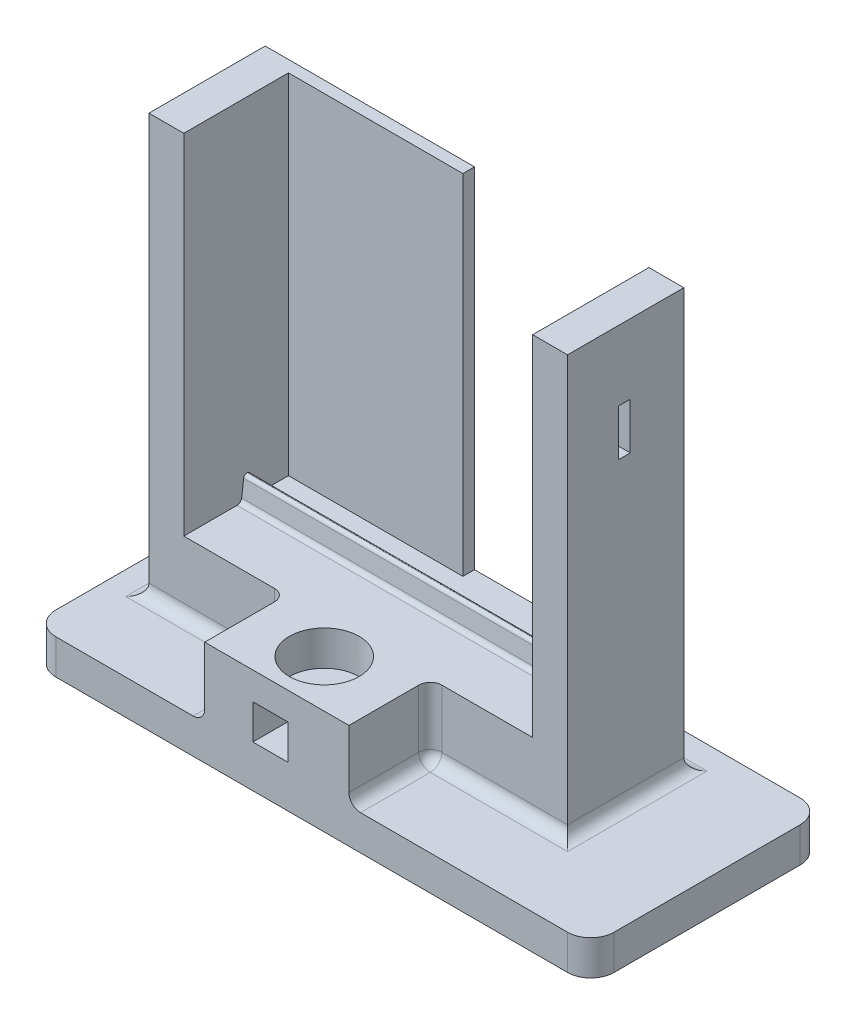
SolidWorks part; units mm, degrees
ref_plane "Front Plane" through (0, 0, 0) normal (0, 0, 1) x (1, 0, 0)
ref_plane "Top Plane" through (0, 0, 0) normal (0, 1, 0) x (1, 0, 0)
ref_plane "Right Plane" through (0, 0, 0) normal (1, 0, 0) x (0, 0, -1)
sketch "Sketch1" plane through (0, 0, 0) normal (0, 1, 0) x (1, 0, 0)
  line L1 (-120, -50) -> (120, -50)
  line L2 (-120, -50) -> (-120, 50)
  line L3 (-120, 50) -> (120, 50)
  line L4 (120, -50) -> (120, 50)
  line L5 (-120, -50) -> (120, 50) construction
  line L6 (-120, 50) -> (120, -50) construction
  point P0 (0, 0)
  dimension "D1" = 240
  dimension "D2" = 100
extrude "Boss-Extrude1" add sketch "Sketch1" along normal blind 15
sketch "Sketch5" plane through (0, 15, 0) normal (0, 1, 0) x (1, 0, 0)
  line L0 (-105, 35) -> (-90, 35)
  line L2 (-105, -15) -> (-90, -15)
  line L4 (-90, 35) -> (-90, -15)
  line L7 (60, 35) -> (60, -15)
  line L10 (60, 35) -> (75, 35)
  line L11 (75, 35) -> (75, -15)
  line L12 (75, -15) -> (60, -15)
  line L13 (-105, 35) -> (-105, -15)
  dimension "D1" = 50
  dimension "D2" = 15
  dimension "D3" = 50
  dimension "D5" = 15
extrude "Boss-Extrude4" add sketch "Sketch5" along normal blind 180
sketch "Sketch12" plane through (0, 15, 0) normal (0, 1, 0) x (1, 0, 0)
  line L0 (60, 35) -> (60, -15) construction
  line L1 (-90, 35) -> (60, 35)
  line L2 (-90, 35) -> (-90, -15)
  line L3 (-90, -15) -> (60, -15)
  line L4 (60, 35) -> (60, -15)
  dimension "D1" = 50
extrude "Boss-Extrude7" add sketch "Sketch12" along normal blind 30
fillet "Fillet1" radius 5 1 edges at (-105, 15, -10)
fillet "Fillet4" radius 5 1 edges at (-17.5, 15, -35)
fillet "Fillet10" radius 5 1 edges at (75, 15, -12.5)
sketch "Sketch15" plane through (0, 15, 0) normal (0, 1, 0) x (1, 0, 0)
  line L0 (-110, -15) -> (80, -15) construction
  line L1 (-15, -15) -> (16, -15)
  line L2 (-15, -15) -> (-46, -15)
  line L3 (-46, -15) -> (-46, -50)
  line L4 (16, -15) -> (16, -50)
  line L5 (-46, -50) -> (16, -50)
  dimension "D1" = 62
  dimension "D2" = 31
  dimension "D3" = 35
extrude "Boss-Extrude8" add sketch "Sketch15" along normal blind 30
sketch "Sketch17" plane through (0, 45, 0) normal (0, 1, 0) x (1, 0, 0)
  circle A0 centre (-15, -29.6274) radius 15
  dimension "D2" = 30
extrude "Cut-Extrude1" cut sketch "Sketch17" against normal blind 15
sketch "Sketch18" plane through (0, 0, 50) normal (0, 0, 1) x (1, 0, 0)
  line L3 (-25.2921, 18.1748) -> (-10.2921, 18.1748)
  line L4 (-25.2921, 18.1748) -> (-25.2921, 33.1748)
  line L5 (-25.2921, 33.1748) -> (-10.2921, 33.1748)
  line L6 (-10.2921, 18.1748) -> (-10.2921, 33.1748)
  line L7 (-25.2921, 18.1748) -> (-10.2921, 33.1748) construction
  line L8 (-25.2921, 33.1748) -> (-10.2921, 18.1748) construction
  dimension "D1" = 15
  dimension "D2" = 15
extrude "Cut-Extrude3" cut sketch "Sketch18" against normal blind 15 contours L3 L6 L5 L4
fillet "Fillet11" radius 5 1 edges at (48, 15, 15)
fillet "Fillet12" radius 5 1 edges at (-78, 15, 15)
fillet "Fillet13" radius 5 3 edges at (16, 32.5, 15) (16, 16.4645, 16.4645) (16, 15, 35)
fillet "Fillet14" radius 5 3 edges at (-46, 32.5, 15) (-46, 16.4645, 16.4645) (-46, 15, 35)
sketch "Sketch23" plane through (60, 0, 0) normal (-1, 0, 0) x (0, 0, 1)
  line L0 (20, 15) -> (-40, 15) construction
  line L1 (-9.66, 45) -> (-14.66, 45)
  line L3 (-13.41, 55) -> (-10.91, 55)
  line L4 (-13.41, 55) -> (-14.66, 45)
  line L5 (-10.91, 55) -> (-9.66, 45)
  point P0 (-12.16, 45)
  dimension "D1" = 30
  dimension "D2" = 5
extrude "Boss-Extrude10" add sketch "Sketch23" along normal blind 150
fillet "Fillet19" radius 1.5 1 edges at (-15, 55, -10.91)
fillet "Fillet20" radius 1.5 1 edges at (-15, 55, -13.41)
sketch "Sketch24" plane through (0, 0, -35) normal (0, 0, -1) x (-1, 0, 0)
  line L0 (15, 45) -> (15, 195)
  line L1 (-60, 45) -> (90, 45) construction
  line L2 (90, 195) -> (15, 195)
  line L3 (15, 45) -> (90, 45)
  line L4 (90, 195) -> (90, 45) construction
  line L5 (90, 195) -> (90, 45)
extrude "Boss-Extrude11" add sketch "Sketch24" against normal blind 5
fillet "Fillet23" radius 2 1 edges at (-15, 45, -9.66)
fillet "Fillet24" radius 2 1 edges at (-15, 45, -14.66)
fillet "Fillet25" radius 10 1 edges at (120, 7.5, 50)
fillet "Fillet26" radius 10 1 edges at (120, 7.5, -50)
fillet "Fillet27" radius 10 1 edges at (-120, 7.5, 50)
fillet "Fillet28" radius 10 1 edges at (-120, 7.5, -50)
sketch "Sketch25" plane through (60, 0, 0) normal (-1, 0, 0) x (0, 0, 1)
  line L0 (-35, 195) -> (15, 195) construction
  line L5 (-11.9624, 165) -> (-6.9624, 165)
  line L6 (-11.9624, 165) -> (-11.9624, 145)
  line L7 (-11.9624, 145) -> (-6.9624, 145)
  line L8 (-6.9624, 165) -> (-6.9624, 145)
  line L9 (-11.9624, 165) -> (-6.9624, 145) construction
  line L10 (-11.9624, 145) -> (-6.9624, 165) construction
  point P2 (-10, 195)
  point P7 (-9.4624, 155)
  dimension "D1" = 5
  dimension "D2" = 20
  dimension "D3" = 30
extrude "Cut-Extrude4" cut sketch "Sketch25" against normal through all
